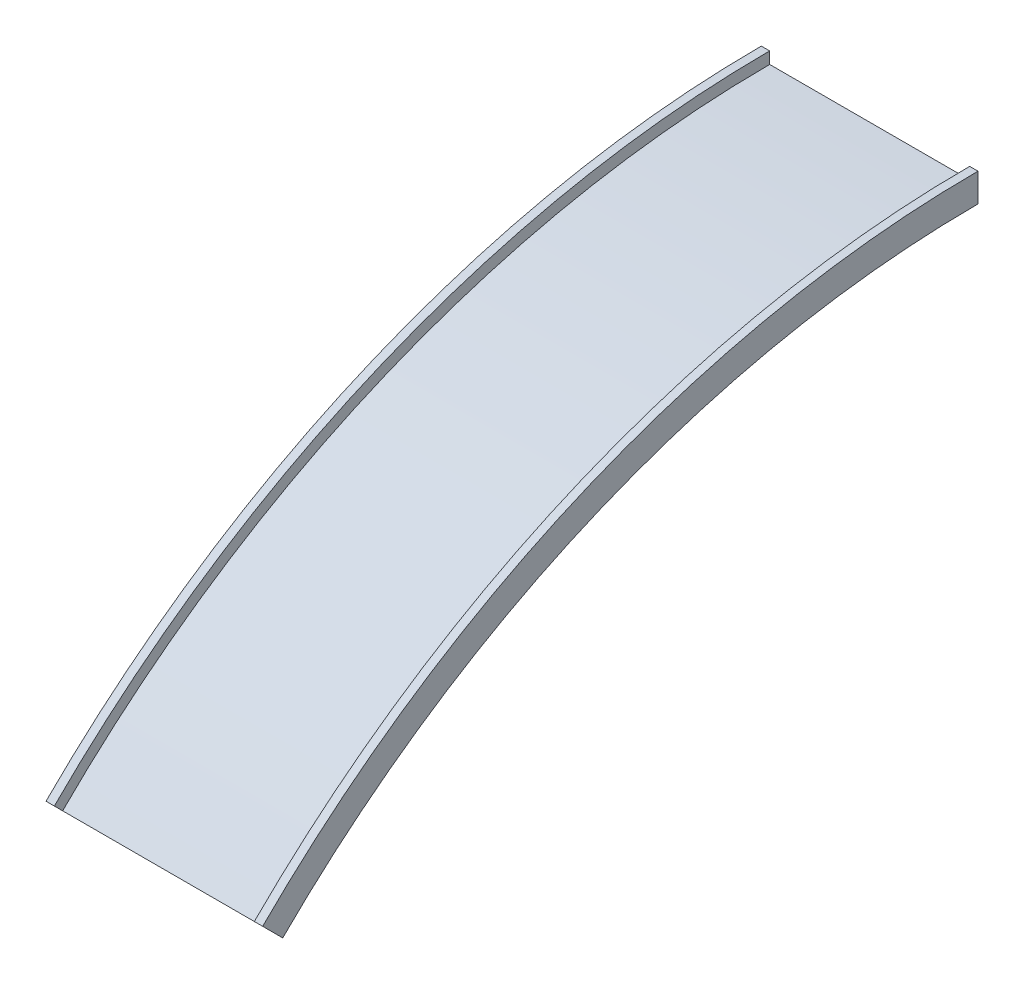
SolidWorks part; units mm, degrees
ref_plane "Front Plane" through (0, 0, 0) normal (0, 0, 1) x (1, 0, 0)
ref_plane "Top Plane" through (0, 0, 0) normal (0, 1, 0) x (1, 0, 0)
ref_plane "Right Plane" through (0, 0, 0) normal (1, 0, 0) x (0, 0, -1)
sketch "Sketch1" plane through (0, 0, 0) normal (0, 0, 1) x (1, 0, 0)
  line L0 (0, 0) -> (25, 0)
  line L1 (25, 0) -> (25, -35.2361)
  line L2 (25, -35.2361) -> (625, -35.2361)
  line L3 (625, -35.2361) -> (625, 0)
  line L4 (625, 0) -> (650, 0)
  line L5 (650, 0) -> (650, -85.2361)
  line L6 (650, -85.2361) -> (0, -85.2361)
  line L7 (0, -85.2361) -> (0, 0)
  line L8 (0, -3035.2361) -> (650, -3035.2361)
  dimension "D1" = 25
  dimension "D2" = 35.2361
  dimension "D3" = 650
  dimension "D4" = 50
  dimension "D5" = 3000
revolve "Revolve2" add sketch "Sketch1" angle 45 about L8
